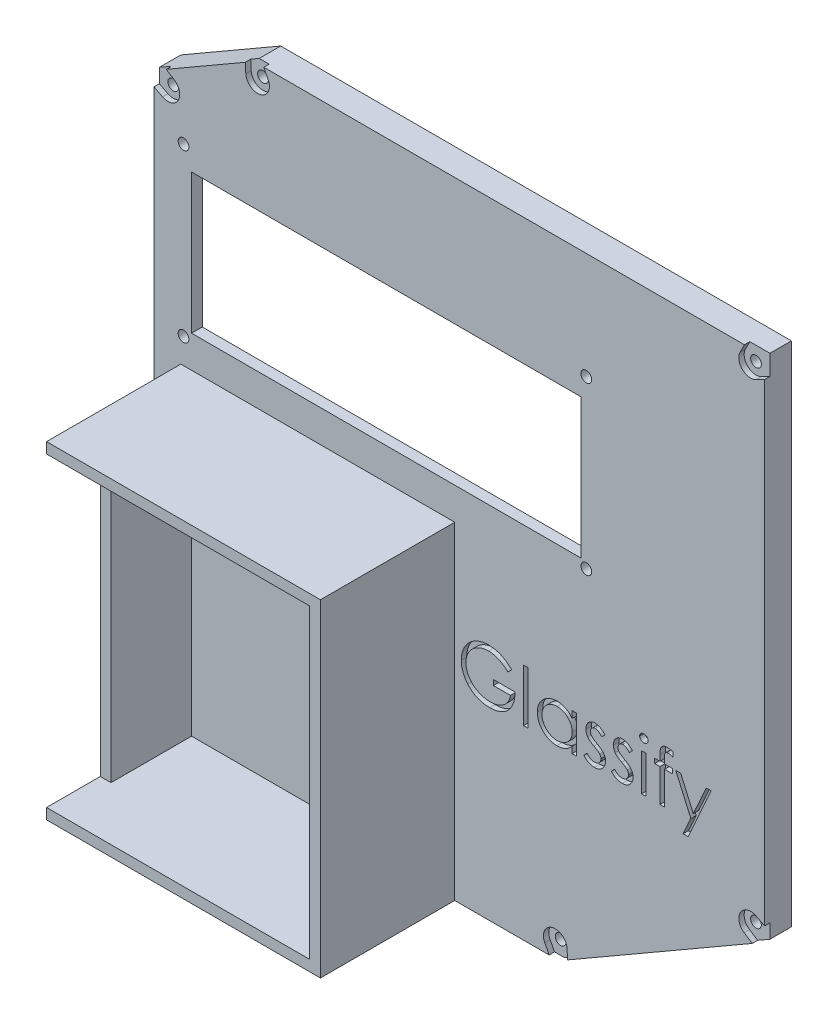
SolidWorks part; units mm, degrees
ref_plane "Front Plane" through (0, 0, 0) normal (0, 0, 1) x (1, 0, 0)
ref_plane "Top Plane" through (0, 0, 0) normal (0, 1, 0) x (1, 0, 0)
ref_plane "Right Plane" through (0, 0, 0) normal (1, 0, 0) x (0, 0, -1)
sketch "Sketch1" plane through (0, 0, 0) normal (0, 0, 1) x (1, 0, 0)
  line L6 (62.85, 287.25) -> (-32.25, 287.25)
  line L7 (62.85, 192.75) -> (62.85, 287.25)
  line L8 (24.5717, 170.65) -> (62.85, 192.75)
  line L9 (-50.85, 170.65) -> (24.5717, 170.65)
  line L10 (-50.85, 276.5113) -> (-50.85, 170.65)
  line L11 (-32.25, 287.25) -> (-50.85, 276.5113)
  line L18 (62.85, 287.25) -> (-32.25, 287.25)
  line L19 (62.85, 192.75) -> (62.85, 287.25)
  line L20 (24.5717, 170.65) -> (62.85, 192.75)
  line L21 (-50.85, 170.65) -> (24.5717, 170.65)
  line L22 (-50.85, 276.5113) -> (-50.85, 170.65)
  line L23 (-32.25, 287.25) -> (-50.85, 276.5113)
  line L24 (-49.25, 273.0506) -> (-49.25, 175.2096)
  line L25 (-33.7504, 284.5362) -> (-47.0529, 276.856)
  line L26 (58.2904, 285.65) -> (-29.5937, 285.65)
  line L27 (61.25, 196.2107) -> (61.25, 282.6904)
  line L28 (26.0721, 173.3638) -> (59.0529, 192.4053)
  line L29 (-46.2904, 172.25) -> (21.9154, 172.25)
  line L30 (-49.25, 273.0506) -> (-49.25, 175.2096)
  line L31 (-33.7504, 284.5362) -> (-47.0529, 276.856)
  line L32 (58.2904, 285.65) -> (-29.5937, 285.65)
  line L33 (61.25, 196.2107) -> (61.25, 282.6904)
  line L34 (26.0721, 173.3638) -> (59.0529, 192.4053)
  line L35 (-46.2904, 172.25) -> (21.9154, 172.25)
  circle A1 centre (-48.25, 173.25) radius 1
  circle A2 centre (-48.25, 173.25) radius 1
  circle A3 centre (-48.25, 275.0102) radius 1
  circle A4 centre (-48.25, 275.0102) radius 1
  circle A5 centre (-31.5533, 284.65) radius 1
  circle A6 centre (-31.5533, 284.65) radius 1
  circle A7 centre (60.25, 194.2511) radius 1
  circle A8 centre (60.25, 194.2511) radius 1
  circle A9 centre (60.25, 284.65) radius 1
  circle A10 centre (60.25, 284.65) radius 1
  circle A11 centre (23.875, 173.25) radius 1
  circle A12 centre (23.875, 173.25) radius 1
  arc A18 (-46.2904, 172.25) -> (-49.25, 175.2096) centre (-48.25, 173.25) ccw
  arc A19 (-49.25, 273.0506) -> (-47.0529, 276.856) centre (-48.25, 275.0102) ccw
  arc A20 (-33.7504, 284.5362) -> (-29.5937, 285.65) centre (-31.5533, 284.65) ccw
  arc A21 (58.2904, 285.65) -> (61.25, 282.6904) centre (60.25, 284.65) ccw
  arc A22 (61.25, 196.2107) -> (59.0529, 192.4053) centre (60.25, 194.2511) ccw
  arc A23 (26.0721, 173.3638) -> (21.9154, 172.25) centre (23.875, 173.25) ccw
  arc A24 (-46.2904, 172.25) -> (-49.25, 175.2096) centre (-48.25, 173.25) ccw
  arc A25 (-49.25, 273.0506) -> (-47.0529, 276.856) centre (-48.25, 275.0102) ccw
  arc A26 (-33.7504, 284.5362) -> (-29.5937, 285.65) centre (-31.5533, 284.65) ccw
  arc A27 (58.2904, 285.65) -> (61.25, 282.6904) centre (60.25, 284.65) ccw
  arc A28 (61.25, 196.2107) -> (59.0529, 192.4053) centre (60.25, 194.2511) ccw
  arc A29 (26.0721, 173.3638) -> (21.9154, 172.25) centre (23.875, 173.25) ccw
  dimension "D1" = 0
  dimension "D2" = 0
  dimension "D3" = 0
  dimension "D4" = 0
  dimension "D5" = 0
  dimension "D6" = 0
  dimension "D7" = 0
  dimension "D8" = 0
extrude "Boss-Extrude1" add sketch "Sketch1" along normal blind 3
sketch "Sketch2" plane through (0, 0, 3) normal (0, 0, 1) x (1, 0, 0)
  line L0 (24.5717, 170.65) -> (62.85, 192.75) construction
  line L1 (-50.85, 170.65) -> (24.5717, 170.65) construction
  line L2 (-50.85, 276.5113) -> (-50.85, 170.65) construction
  line L3 (-32.25, 287.25) -> (-50.85, 276.5113) construction
  line L4 (62.85, 287.25) -> (-32.25, 287.25) construction
  line L5 (62.85, 192.75) -> (62.85, 287.25) construction
  line L6 (24.5717, 170.65) -> (62.85, 192.75)
  line L7 (-50.85, 170.65) -> (24.5717, 170.65)
  line L8 (-50.85, 276.5113) -> (-50.85, 170.65)
  line L9 (-32.25, 287.25) -> (-50.85, 276.5113)
  line L10 (62.85, 287.25) -> (-32.25, 287.25)
  line L11 (62.85, 192.75) -> (62.85, 287.25)
extrude "Boss-Extrude2" add sketch "Sketch2" along normal blind 2
sketch "Sketch3" plane through (0, 0, 5) normal (0, 0, 1) x (1, 0, 0)
  line L1 (-47.85, 269.8843) -> (32.15, 269.8843) construction
  line L2 (-47.85, 269.8843) -> (-47.85, 233.8843) construction
  line L3 (-47.85, 233.8843) -> (32.15, 233.8843) construction
  line L4 (32.15, 269.8843) -> (32.15, 233.8843) construction
  line L5 (-50.85, 170.65) -> (24.5717, 170.65) construction
  line L6 (-47.85, 228.65) -> (-2.85, 228.65) construction
  line L7 (-47.85, 228.65) -> (-47.85, 173.65) construction
  line L8 (-47.85, 173.65) -> (-2.85, 173.65) construction
  line L9 (-2.85, 228.65) -> (-2.85, 173.65) construction
  line L10 (-50.85, 276.5113) -> (-50.85, 170.65) construction
  dimension "D1" = 80
  dimension "D2" = 36
  dimension "D3" = 55
  dimension "D4" = 45
  dimension "D5" = 3
  dimension "D6" = 3
sketch "Sketch4" plane through (0, 0, 3) normal (0, 0, -1) x (-1, 0, 0)
  line L1 (-28.65, 263.6343) -> (43.85, 263.6343)
  line L2 (-28.65, 263.6343) -> (-28.65, 237.6343)
  line L3 (-28.65, 237.6343) -> (43.85, 237.6343)
  line L4 (43.85, 263.6343) -> (43.85, 237.6343)
  dimension "D1" = 26
  dimension "D2" = 72.5
  dimension "D3" = 6.25
  dimension "D4" = 3.5
extrude "Cut-Extrude1" cut sketch "Sketch4" against normal up to surface (2 mm away) up to face at (2.7203, 230.8435, 5)
sketch "Sketch5" plane through (0, 0, 3) normal (0, 0, -1) x (-1, 0, 0)
  line L0 (47.85, 269.8843) -> (47.85, 233.8843) construction
  line L1 (-32.15, 269.8843) -> (-32.15, 233.8843) construction
  line L2 (47.85, 269.8843) -> (-32.15, 269.8843) construction
  line L3 (47.85, 233.8843) -> (-32.15, 233.8843) construction
  line L4 (47.85, 228.65) -> (2.85, 228.65) construction
  line L5 (47.85, 228.65) -> (47.85, 173.65) construction
  line L6 (47.85, 173.65) -> (2.85, 173.65) construction
  line L7 (2.85, 228.65) -> (2.85, 173.65) construction
  line L8 (47.85, 228.65) -> (2.85, 228.65) construction
  line L9 (47.85, 228.65) -> (47.85, 173.65) construction
  line L10 (47.85, 173.65) -> (2.85, 173.65) construction
  line L11 (2.85, 228.65) -> (2.85, 173.65) construction
  line L13 (5.35, 226.15) -> (30.35, 226.15)
  line L14 (5.35, 226.15) -> (5.35, 224.15)
  line L15 (5.35, 224.15) -> (30.35, 224.15)
  line L16 (30.35, 226.15) -> (30.35, 224.15)
  circle A0 centre (45.35, 267.3843) radius 1
  circle A1 centre (45.35, 236.3843) radius 1
  circle A2 centre (-29.65, 267.3843) radius 1
  circle A3 centre (-29.65, 236.3843) radius 1
  dimension "D5" = 2
  dimension "D1" = 2.5
  dimension "D2" = 2.5
  dimension "D3" = 2.5
  dimension "D4" = 2.5
  dimension "D6" = 25
  dimension "D7" = 2
  dimension "D8" = 2.5
  dimension "D9" = 2.5
extrude "Cut-Extrude2" cut sketch "Sketch5" against normal up to surface (2 mm away) up to face at (-7.6, 250.6343, 5)
sketch "Sketch6" plane through (0, 0, 5) normal (0, 0, 1) x (1, 0, 0)
  line L0 (-50.85, 170.65) -> (24.5717, 170.65) construction
  line L2 (-50.85, 276.5113) -> (-50.85, 170.65) construction
  line L4 (-42.85, 173.65) -> (2.15, 173.65) construction
  line L5 (2.15, 228.65) -> (2.15, 173.65) construction
  line L6 (-42.85, 228.65) -> (2.15, 228.65) construction
  line L7 (-42.85, 228.65) -> (-42.85, 173.65) construction
  line L8 (-43.85, 172.65) -> (3.15, 172.65)
  line L9 (3.15, 229.65) -> (3.15, 172.65)
  line L10 (-43.85, 229.65) -> (3.15, 229.65)
  line L11 (-43.85, 229.65) -> (-43.85, 172.65)
  line L12 (-45.85, 231.65) -> (5.15, 231.65)
  line L13 (5.15, 231.65) -> (5.15, 170.65)
  line L14 (-45.85, 170.65) -> (5.15, 170.65)
  line L15 (-45.85, 231.65) -> (-45.85, 170.65)
  dimension "D3" = 45
  dimension "D4" = 55
  dimension "D5" = 5
  dimension "D1" = 1
  dimension "D2" = 2
extrude "Boss-Extrude3" add sketch "Sketch6" along normal blind 25
sketch "Sketch7" plane through (-50.85, 0, 0) normal (-1, 0, 0) x (0, 0, 1)
  line L0 (30, 172.65) -> (30, 229.65) construction
  line L1 (30, 172.65) -> (30, 229.65)
  line L2 (30, 229.65) -> (20, 229.65)
  line L3 (20, 229.65) -> (20, 172.65)
  line L4 (20, 172.65) -> (30, 172.65)
  dimension "D1" = 10
extrude "Cut-Extrude3" cut sketch "Sketch7" against normal blind 25
sketch "Sketch8" plane through (0, 0, 5) normal (0, 0, 1) x (1, 0, 0)
  line L0 (61.25, 196.2107) -> (62.85, 195.3942)
  line L1 (62.85, 192.75) -> (62.85, 287.25) construction
  line L2 (62.85, 195.3942) -> (62.85, 192.75)
  line L3 (62.85, 192.75) -> (60.5601, 191.4279)
  line L4 (24.5717, 170.65) -> (62.85, 192.75) construction
  line L5 (60.5601, 191.4279) -> (59.0529, 192.4053)
  line L6 (26.0721, 173.3638) -> (26.165, 171.5699)
  line L7 (26.165, 171.5699) -> (24.5717, 170.65)
  line L8 (24.5717, 170.65) -> (22.7319, 170.65)
  line L9 (5.15, 170.65) -> (24.5717, 170.65) construction
  line L10 (22.7319, 170.65) -> (21.9154, 172.25)
  line L11 (-46.2904, 172.25) -> (-47.1069, 170.65)
  line L18 (-46.2904, 172.25) -> (21.9154, 172.25)
  line L19 (-49.25, 273.0506) -> (-49.25, 175.2096)
  line L20 (-33.7504, 284.5362) -> (-47.0529, 276.856)
  line L21 (58.2904, 285.65) -> (-29.5937, 285.65)
  line L22 (61.25, 196.2107) -> (61.25, 282.6904)
  line L23 (26.0721, 173.3638) -> (59.0529, 192.4053)
  line L30 (-50.85, 170.65) -> (24.5717, 170.65) construction
  line L31 (-47.1069, 170.65) -> (-50.85, 170.65)
  line L32 (-50.85, 170.65) -> (-50.85, 174.3931)
  line L33 (-50.85, 276.5113) -> (-50.85, 170.65) construction
  line L34 (-50.85, 174.3931) -> (-49.25, 175.2096)
  line L35 (-47.0529, 276.856) -> (-48.5601, 277.8334)
  line L36 (-32.25, 287.25) -> (-50.85, 276.5113) construction
  line L37 (-48.5601, 277.8334) -> (-50.85, 276.5113)
  line L38 (-50.85, 276.5113) -> (-50.85, 273.8671)
  line L39 (-50.85, 276.5113) -> (-50.85, 170.65) construction
  line L40 (-50.85, 273.8671) -> (-49.25, 273.0506)
  line L41 (-29.5937, 285.65) -> (-30.4102, 287.25)
  line L42 (62.85, 287.25) -> (-32.25, 287.25) construction
  line L43 (-30.4102, 287.25) -> (-32.25, 287.25)
  line L44 (-32.25, 287.25) -> (-33.8433, 286.3301)
  line L45 (-50.85, 276.5113) -> (-32.25, 287.25) construction
  line L46 (-33.8433, 286.3301) -> (-33.7504, 284.5362)
  line L47 (58.2904, 285.65) -> (59.1069, 287.25)
  line L48 (59.1069, 287.25) -> (62.85, 287.25)
  line L49 (62.85, 287.25) -> (62.85, 283.5069)
  line L50 (62.85, 283.5069) -> (61.25, 282.6904)
  circle A1 centre (-48.25, 275.0102) radius 1
  circle A2 centre (-48.25, 275.0102) radius 1
  circle A3 centre (-48.25, 173.25) radius 1
  circle A4 centre (-48.25, 173.25) radius 1
  circle A5 centre (23.875, 173.25) radius 1
  circle A6 centre (23.875, 173.25) radius 1
  circle A7 centre (60.25, 284.65) radius 1
  circle A8 centre (60.25, 284.65) radius 1
  circle A9 centre (60.25, 194.2511) radius 1
  circle A10 centre (60.25, 194.2511) radius 1
  circle A11 centre (-31.5533, 284.65) radius 1
  circle A12 centre (-31.5533, 284.65) radius 1
  arc A18 (-46.2904, 172.25) -> (-49.25, 175.2096) centre (-48.25, 173.25) ccw
  arc A19 (-49.25, 273.0506) -> (-47.0529, 276.856) centre (-48.25, 275.0102) ccw
  arc A20 (-33.7504, 284.5362) -> (-29.5937, 285.65) centre (-31.5533, 284.65) ccw
  arc A21 (58.2904, 285.65) -> (61.25, 282.6904) centre (60.25, 284.65) ccw
  arc A22 (61.25, 196.2107) -> (59.0529, 192.4053) centre (60.25, 194.2511) ccw
  arc A23 (26.0721, 173.3638) -> (21.9154, 172.25) centre (23.875, 173.25) ccw
  arc A24 (-46.2904, 172.25) -> (-49.25, 175.2096) centre (-48.25, 173.25) ccw
  arc A25 (-49.25, 273.0506) -> (-47.0529, 276.856) centre (-48.25, 275.0102) ccw
  arc A26 (-33.7504, 284.5362) -> (-29.5937, 285.65) centre (-31.5533, 284.65) ccw
  arc A27 (58.2904, 285.65) -> (61.25, 282.6904) centre (60.25, 284.65) ccw
  arc A28 (61.25, 196.2107) -> (59.0529, 192.4053) centre (60.25, 194.2511) ccw
  arc A29 (26.0721, 173.3638) -> (21.9154, 172.25) centre (23.875, 173.25) ccw
  text T0 "Glassify" font "Century Gothic" height in points 36
  dimension "D1" = 0
  dimension "D2" = 0
  dimension "D4" = 0
  dimension "D5" = 0
  dimension "D6" = 0
  dimension "D7" = 0
  dimension "D8" = 0
extrude "Cut-Extrude4" cut sketch "Sketch8" against normal blind 1
extrude "Cut-Extrude5" cut sketch "Sketch8<2>" against normal through all both and the other way through all contours A4 | A10 | A6 | A2 | A12 | A8 region at (-48.25, 173.25, 5)
sketch "Sketch8<2>" plane through (0, 0, 5) normal (0, 0, 1) x (1, 0, 0) same geometry as "Sketch8"
